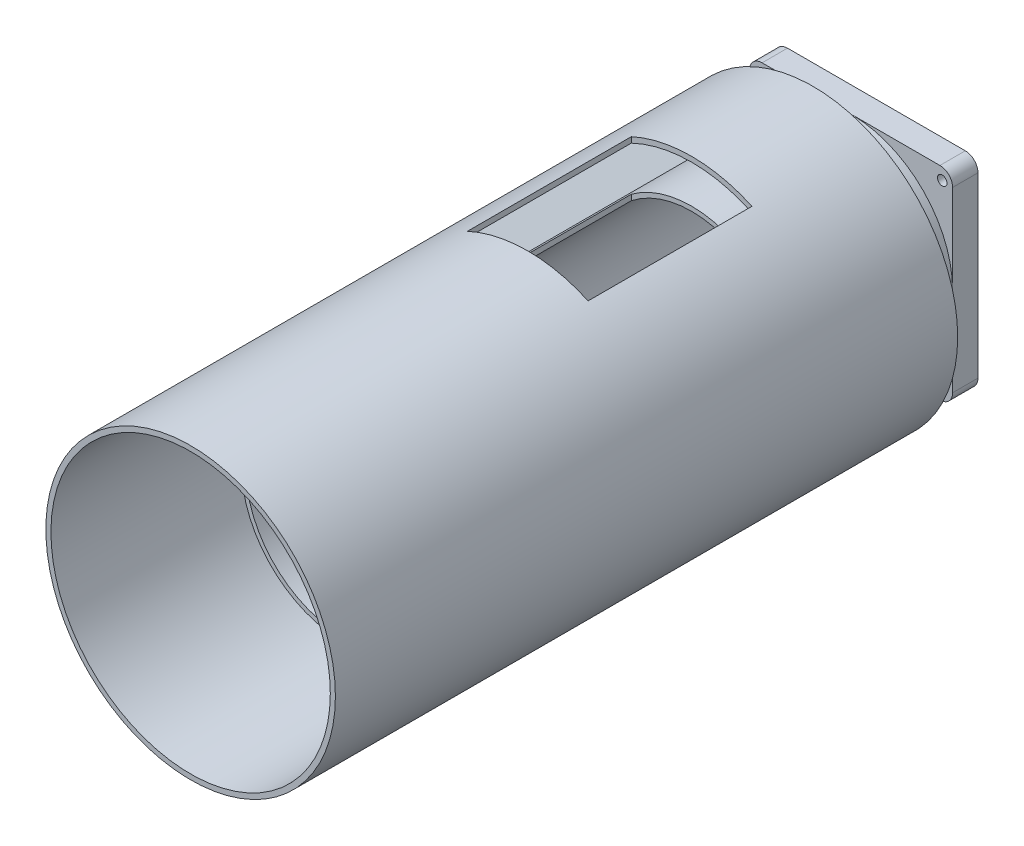
SolidWorks part; units mm, degrees
ref_plane "前视基准面" through (0, 0, 0) normal (0, 0, 1) x (1, 0, 0)
ref_plane "上视基准面" through (0, 0, 0) normal (0, 1, 0) x (1, 0, 0)
ref_plane "右视基准面" through (0, 0, 0) normal (1, 0, 0) x (0, 0, -1)
ref_axis "基准轴1" through (0, 0, 20.9) along (0, 0, -1)
ref_plane "基准面1" through (55, 0, 0) normal (1, 0, 0) x (0, 0, -1)
sketch "草图7" plane through (0, 0, 0) normal (0, 0, 1) x (1, 0, 0)
  line L1 (-40, 40) -> (40, 40)
  line L2 (-40, 40) -> (-40, -40)
  line L3 (-40, -40) -> (40, -40)
  line L4 (40, 40) -> (40, -40)
  line L5 (-40, 40) -> (40, -40) construction
  line L6 (-40, -40) -> (40, 40) construction
  circle A0 centre (0, 0) radius 50.7986 construction
  circle A1 centre (-35.92, 35.92) radius 1.875
  circle A2 centre (35.92, 35.92) radius 1.875
  circle A3 centre (35.92, -35.92) radius 1.875
  circle A4 centre (-35.92, -35.92) radius 1.875
  circle A5 centre (0, 0) radius 38.25
  point P0 (0, 0)
  point P17 (0, 38.25)
  dimension "D2" = 3.75
  dimension "D4" = 76.5
  dimension "D1" = 80
  dimension "D3" = 71.84
extrude "凸台-拉伸3" [suppressed] add sketch "草图7" along normal mid plane 25 contours A5 | L4 L1 L2 L3 A5 A4 A3 A2 A1
fillet "圆角1" [suppressed] radius 5
sketch "草图2" [suppressed] plane through (0, 0, 0) normal (0, 1, 0) x (1, 0, 0)
  line L0 (0, 12.5) -> (0, -12.5) construction
  line L1 (0, 0) -> (89.5, 0) construction
  line L3 (89.5, -8.5) -> (39.5, -8.5)
  line L4 (89.5, -8.5) -> (89.5, 8.5)
  line L5 (89.5, 8.5) -> (39.5, 8.5)
  line L6 (39.5, -8.5) -> (39.5, 8.5)
  line L7 (38.25, 4.5) -> (17.5, 4.5)
  line L8 (38.25, 4.5) -> (38.25, -12.5)
  line L9 (38.25, -12.5) -> (14.5, -12.5)
  line L10 (14.5, -12.5) -> (0, -12.5)
  line L12 (17.5, 4.5) -> (17.5, -9.5)
  line L14 (-35, 12.5) -> (35, 12.5) construction
  arc A2 (14.5, -12.5) -> (17.5, -9.5) centre (14.5, -9.5) ccw
  point P14 (38.25, 0)
  dimension "D8" = 3
  dimension "D1" = 4
  dimension "D2" = 79
  dimension "D3" = 50
  dimension "D4" = 8
  dimension "D6" = 35
revolve "切除-旋转1" [suppressed] cut sketch "草图2" angle 360 about L0
sketch "草图3" [suppressed] plane through (0, 0, 0) normal (0, 0, 1) x (1, 0, 0)
  line L0 (0, 0) -> (0, 17.5) construction
  line L1 (8.0065, 15.561) -> (38.25, 0)
  line L3 (9.473, -14.7144) -> (-19.125, -33.1255)
  line L4 (-17.4795, -0.8466) -> (-19.125, 33.1255)
  line L5 (37.8635, -5.4241) -> (16.6094, 5.5116)
  circle A0 centre (0, 0) radius 17.5
  arc A1 (-19.125, -33.1255) -> (38.25, 0) centre (0, 0) ccw
  circle A2 centre (0, 0) radius 38.25 construction
  point P17 (0, 0)
  dimension "D2" = 5
  dimension "D1" = 3
extrude "切除-拉伸1" [suppressed] cut sketch "草图3" against normal through all contours L3 A1 L5 A0
pattern_circular "阵列(圆周)1" [suppressed] count 3 over 360 about axis through (0, 0, 20.9) along (0, 0, -1) of bodies 108
sketch "草图4" plane through (0, 0, 0) normal (1, 0, 0) x (0, 0, -1)
  line L0 (-14.3137, 11.3137) -> (8.3137, -11.3137) construction
  line L1 (-13.4298, 12.1976) -> (9.1976, -10.4298)
  line L2 (-15.1976, 10.4298) -> (7.4298, -12.1976)
  line L3 (-20.9, 0) -> (20.9, 0) construction
  arc A0 (-13.4298, 12.1976) -> (-15.1976, 10.4298) centre (-14.3137, 11.3137) ccw
  arc A1 (7.4298, -12.1976) -> (9.1976, -10.4298) centre (8.3137, -11.3137) ccw
  point P2 (-3, 0)
  dimension "D1" = 2.5
  dimension "D2" = 45
  dimension "D3" = 32
  dimension "D4" = 3
sketch "草图5" plane through (55, 0, 0) normal (1, 0, 0) x (0, 0, -1)
  line L0 (-11.8163, 50) -> (5.8163, -50) construction
  line L1 (-10.5853, 50.2171) -> (7.0474, -49.7829)
  line L2 (-13.0474, 49.7829) -> (4.5853, -50.2171)
  line L3 (-20.9, 0) -> (20.9, 0) construction
  arc A0 (-10.5853, 50.2171) -> (-13.0474, 49.7829) centre (-11.8163, 50) ccw
  arc A1 (4.5853, -50.2171) -> (7.0474, -49.7829) centre (5.8163, -50) ccw
  arc A2 (-13.4298, 12.1976) -> (-15.1976, 10.4298) centre (-14.3137, 11.3137) ccw construction
  point P2 (-3, 0)
  dimension "D1" = 80
  dimension "D2" = 100
loft "放样1" [suppressed] add profiles "草图4", "草图5"
sketch "草图6" [suppressed] plane through (0, 0, 0) normal (0, 0, 1) x (1, 0, 0)
  line L0 (0, 11.3137) -> (0, -11.3137) construction
  line L1 (0, 0) -> (19.8943, -19.8943)
  line L2 (0, 0) -> (19.3185, 5.1764)
  line L3 (0, -65.4206) -> (0, 62.9965) construction
  line L5 (0, 0) -> (112.9869, 0) construction
  arc A0 (37.2417, -0.7851) -> (32.5394, -18.1314) centre (0, 0) cw
  arc A1 (32.466, 1.6957) -> (19.3185, 5.1764) centre (27.2947, 8.7333) cw
  arc A2 (32.5394, -18.1314) -> (19.8943, -19.8943) centre (25.5511, -14.2374) cw
  arc A3 (37.2417, -0.7851) -> (32.466, 1.6957) centre (34.2424, -0.7219) ccw
  circle A4 centre (0, 0) radius 38.25 construction
  point P17 (35.9807, 9.641)
  dimension "D1" = 60
  dimension "D3" = 8
  dimension "D4" = 1
  dimension "D6" = 3
  dimension "D2" = 45
  dimension "D5" = 20
extrude "切除-拉伸2" [suppressed] cut sketch "草图6" against normal mid plane 100 flip side to cut contours A0 A3 A1 L2 L1 A2
pattern_circular "阵列(圆周)3" [suppressed] count 5 over 360 about axis through (0, 0, 20.9) along (0, 0, -1) of bodies 111 112
fillet "圆角2" [suppressed] radius 3
sketch "Sketch1" plane through (0, 0, 0) normal (0, 0, 1) x (1, 0, 0)
  line L0 (0, -40) -> (0, 40) construction
  line L1 (-40, 0) -> (40, 0) construction
  line L8 (35, 40) -> (-35, 40)
  line L9 (-40, 35.0014) -> (-40, -34.9986)
  line L10 (-35, -40) -> (35, -40)
  line L11 (40, -34.9986) -> (40, 35.0014)
  arc A9 (-35, 40) -> (-40, 35.0014) centre (-35, 35) ccw
  arc A10 (-40, -34.9986) -> (-35, -40) centre (-35, -35) ccw
  arc A11 (35, -40) -> (40, -34.9986) centre (35, -35) ccw
  arc A12 (40, 35.0014) -> (35, 40) centre (35, 35) ccw
  circle A13 centre (-35.92, 35.336) radius 1.875
  circle A14 centre (-35.92, -35.92) radius 1.875
  circle A15 centre (35.92, 35.336) radius 1.875
  circle A16 centre (35.92, -35.92) radius 1.875
  circle A17 centre (0, 0) radius 38.25
  point P16 (0, 0)
  point P30 (0, 0)
  dimension "D2" = 5
  dimension "D3" = 3.75
  dimension "D6" = 76.5
  dimension "D10" = 5
  dimension "D1" = 70
  dimension "D4" = 40
  dimension "D5" = 50.7986
  dimension "D7" = 40
  dimension "D8" = 1.3011
  dimension "D9" = 35.336
extrude "Boss-Extrude1" add sketch "Sketch1" along normal mid plane 10 separate body
sketch "Sketch2" plane through (0, 0, 5) normal (0, 0, 1) x (1, 0, 0)
  circle A0 centre (0, 0) radius 40
  circle A1 centre (0, 0) radius 38.25 construction
  circle A2 centre (0, 0) radius 38.25
  dimension "D1" = 80
extrude "Boss-Extrude2" add sketch "Sketch2" along normal blind 200 separate body
ref_plane "Plane1" through (0, 0, 20) normal (0, 0, 1) x (1, 0, 0)
sketch "Sketch3" plane through (0, 0, 20) normal (0, 0, 1) x (1, 0, 0)
  line L0 (0, -38.25) -> (0, -55) construction
  line L1 (-1.75, -38.2099) -> (-1.75, -54.9722)
  line L2 (1.75, -38.2099) -> (1.75, -54.9722)
  line L3 (-33.1255, 19.125) -> (-47.6314, 27.5) construction
  line L4 (-32.2158, 20.6205) -> (-46.7323, 29.0016)
  line L5 (-33.9658, 17.5894) -> (-48.4823, 25.9705)
  line L6 (33.1255, 19.125) -> (47.6314, 27.5) construction
  line L7 (33.9658, 17.5894) -> (48.4823, 25.9705)
  line L8 (32.2158, 20.6205) -> (46.7323, 29.0016)
  circle A0 centre (0, 0) radius 55
  circle A1 centre (0, 0) radius 57
  circle A2 centre (0, 0) radius 38.25 construction
  circle A3 centre (0, 0) radius 38.25
  dimension "D1" = 110
  dimension "D3" = 1.75
  dimension "D2" = 2
  dimension "D4" = 3
extrude "Boss-Extrude3" add sketch "Sketch3" along normal through all separate body contours A1 A0 | A3 L1 A0 L2 | A3 L4 A0 L5 | A3 L7 A0 L8 region at (0, -46.6137, 20) region at (-40.3686, 23.3068, 20) region at (40.3686, 23.3068, 20) region at (-55.3878, 0, 20)
sketch "Sketch4" plane through (0, 0, 0) normal (0, 1, 0) x (1, 0, 0)
  line L0 (-57, -205) -> (57, -205) construction
  line L1 (57, -20) -> (-57, -20) construction
  line L2 (-57, -205) -> (57, -205)
  line L3 (57, -20) -> (-57, -20)
  line L4 (0, 5) -> (0, -205) construction
  line L6 (-23.75, -67.75) -> (23.75, -67.75)
  line L7 (-23.75, -67.75) -> (-23.75, -132.25)
  line L8 (-23.75, -132.25) -> (23.75, -132.25)
  line L9 (23.75, -67.75) -> (23.75, -132.25)
  line L10 (-23.75, -67.75) -> (23.75, -132.25) construction
  line L11 (-23.75, -132.25) -> (23.75, -67.75) construction
  line L13 (35, 5) -> (-35, 5) construction
  line L14 (35, 5) -> (-35, 5)
  point P4 (0, -100)
  point P7 (0, -100)
  point P20 (0, 5)
  dimension "D1" = 47.5
  dimension "D2" = 64.5
extrude "Cut-Extrude1" cut sketch "Sketch4" along normal through all contours L9 L6 L7 L8 region at (0, 0, 100)
ref_plane "Plane2" through (0, 0, 132.25) normal (0, 0, -1) x (-1, 0, 0)
sketch "Sketch5" plane through (0, 0, 132.25) normal (0, 0, -1) x (-1, 0, 0)
  line L0 (-23.75, 32.186) -> (-23.75, 29.9833) construction
  line L1 (23.75, 29.9833) -> (23.75, 32.186) construction
  line L2 (23.75, 49.6078) -> (23.75, 51.8164) construction
  line L3 (-23.75, 51.8164) -> (-23.75, 49.6078) construction
  line L4 (-23.75, 32.186) -> (-23.75, 29.9833)
  line L5 (23.75, 29.9833) -> (23.75, 32.186)
  line L6 (23.75, 49.6078) -> (23.75, 51.8164)
  line L7 (-23.75, 51.8164) -> (-23.75, 49.6078)
  line L8 (-23.75, 49.6078) -> (-23.75, 32.186)
  line L9 (23.75, 49.6078) -> (23.75, 32.186)
  arc A0 (23.75, 32.186) -> (-23.75, 32.186) centre (0, 0) ccw construction
  arc A1 (23.75, 29.9833) -> (-23.75, 29.9833) centre (0, 0) ccw construction
  arc A2 (23.75, 51.8164) -> (-23.75, 51.8164) centre (0, 0) ccw construction
  arc A3 (23.75, 49.6078) -> (-23.75, 49.6078) centre (0, 0) ccw construction
  arc A4 (23.75, 32.186) -> (-23.75, 32.186) centre (0, 0) ccw
  arc A5 (23.75, 29.9833) -> (-23.75, 29.9833) centre (0, 0) ccw
  arc A6 (23.75, 51.8164) -> (-23.75, 51.8164) centre (0, 0) ccw
  arc A7 (23.75, 49.6078) -> (-23.75, 49.6078) centre (0, 0) ccw
extrude "Boss-Extrude4" add sketch "Sketch5" against normal blind 2 contours L9 A7 L8 A4 region at (0, 45.287, 132.25)
sketch "Sketch6" plane through (0, 0, 205) normal (0, 0, 1) x (1, 0, 0)
  circle A0 centre (0, 0) radius 57 construction
  circle A1 centre (0, 0) radius 57
  circle A2 centre (0, 0) radius 55
  arc M6 (-46.7323, 29.0016) -> (46.7323, 29.0016) centre (0, 0) cw
  arc M10 (-1.75, -54.9722) -> (-48.4823, 25.9705) centre (0, 0) cw
  arc M14 (48.4823, 25.9705) -> (1.75, -54.9722) centre (0, 0) cw
  circle M16 centre (0, 0) radius 57
extrude "Boss-Extrude5" add sketch "Sketch6" along normal blind 60 contours A2 M16 M14 M10 M6 | A1 | A2 region at (-55.3878, 0, 205)
